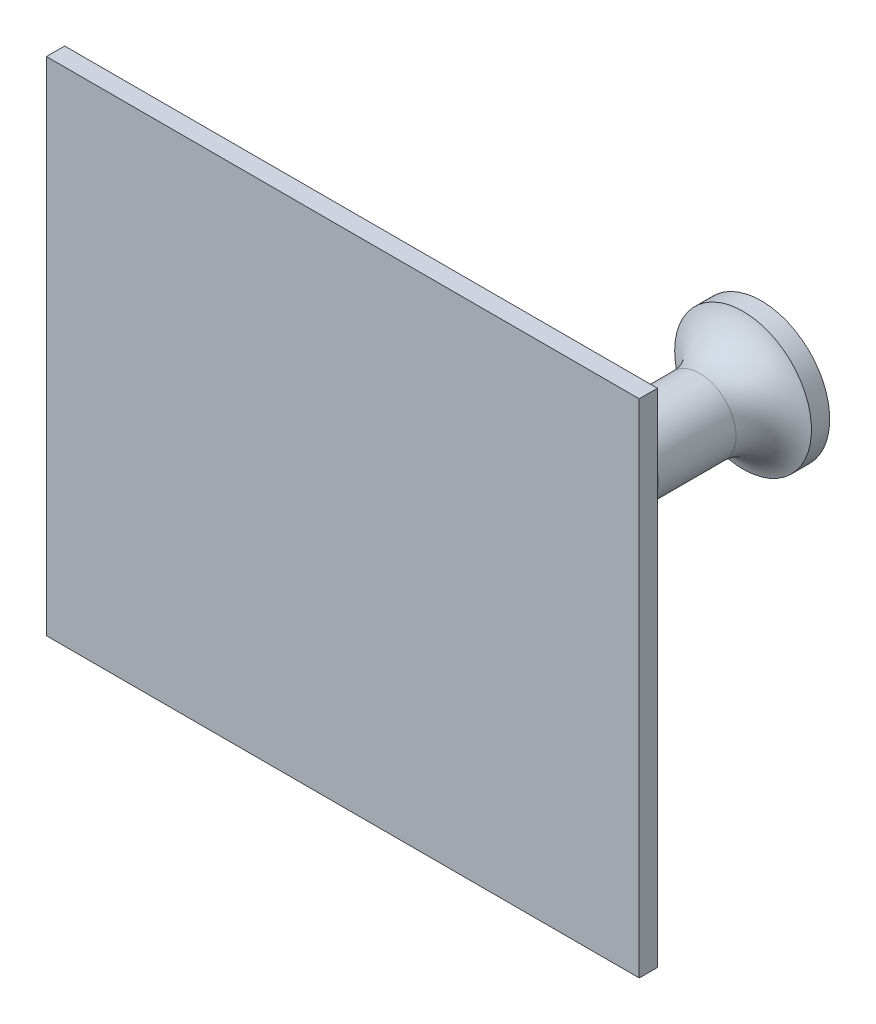
SolidWorks part; units mm, degrees
ref_plane "Ebene vorne" through (0, 0, 0) normal (0, 0, 1) x (1, 0, 0)
ref_plane "Ebene oben" through (0, 0, 0) normal (0, 1, 0) x (1, 0, 0)
ref_plane "Ebene rechts" through (0, 0, 0) normal (1, 0, 0) x (0, 0, -1)
sketch "Skizze2" plane through (0, 0, 0) normal (0, 0, 1) x (1, 0, 0)
  line L1 (-32.5, 50) -> (32.5, 50)
  line L2 (-32.5, 50) -> (-32.5, -50)
  line L3 (-32.5, -50) -> (32.5, -50)
  line L4 (32.5, 50) -> (32.5, -50)
  line L5 (-32.5, 50) -> (32.5, -50) construction
  line L6 (-32.5, -50) -> (32.5, 50) construction
  point P0 (0, 0)
  dimension "D1" = 65
  dimension "D2" = 100
extrude "Aufsatz-Linear austragen1" add sketch "Skizze2" along normal blind 2
sketch "Skizze3" plane through (9.8844, -5.6468, 0) normal (0, 0, -1) x (-1, 0, 0)
  circle A0 centre (0, 28.1496) radius 4
  dimension "D1" = 8
extrude "Aufsatz-Linear austragen2" add sketch "Skizze3" along normal blind 15
sketch "Skizze4" plane through (9.8844, -5.6468, -15) normal (0, 0, -1) x (-1, 0, 0)
  circle A0 centre (0, 28.1496) radius 5
  dimension "D1" = 10
extrude "Aufsatz-Linear austragen3" add sketch "Skizze4" along normal blind 2
sketch "Skizze5" plane through (9.8844, -5.6468, -17) normal (0, 0, -1) x (-1, 0, 0)
  circle A0 centre (0, 28.1496) radius 4
  dimension "D1" = 8
extrude "Aufsatz-Linear austragen4" add sketch "Skizze5" along normal blind 15
sketch "Skizze6" plane through (9.8844, -5.6468, -32) normal (0, 0, -1) x (-1, 0, 0)
  circle A0 centre (0, 28.1496) radius 7.5
  dimension "D1" = 15
extrude "Aufsatz-Linear austragen5" add sketch "Skizze6" along normal blind 2
fillet "Verrundung1" radius 2 1 edges at (5.8844, 22.5027, -15)
fillet "Verrundung2" radius 2 1 edges at (5.8844, 22.5027, -17)
fillet "Verrundung3" radius 5 1 edges at (5.8844, 22.5027, -32)
sketch "Skizze7" plane through (0, 0, 0) normal (0, 0, -1) x (-1, 0, 0)
  line L0 (-32.5, -50) -> (-32.5, 50) construction
  line L1 (-32.5, -5) -> (32.5, -5)
  line L2 (-32.5, -5) -> (-32.5, -50)
  line L3 (-32.5, -50) -> (32.5, -50)
  line L4 (32.5, -5) -> (32.5, -50)
  line L5 (32.5, 50) -> (32.5, -50) construction
  dimension "D1" = 45
extrude "Schnitt-Linear austragen1" cut sketch "Skizze7" against normal blind 2
sketch "Skizze8" plane through (0, 0, 0) normal (0, 0, -1) x (-1, 0, 0)
fillet "Verrundung4" radius 2 1 edges at (13.8844, 22.5027, 0)
